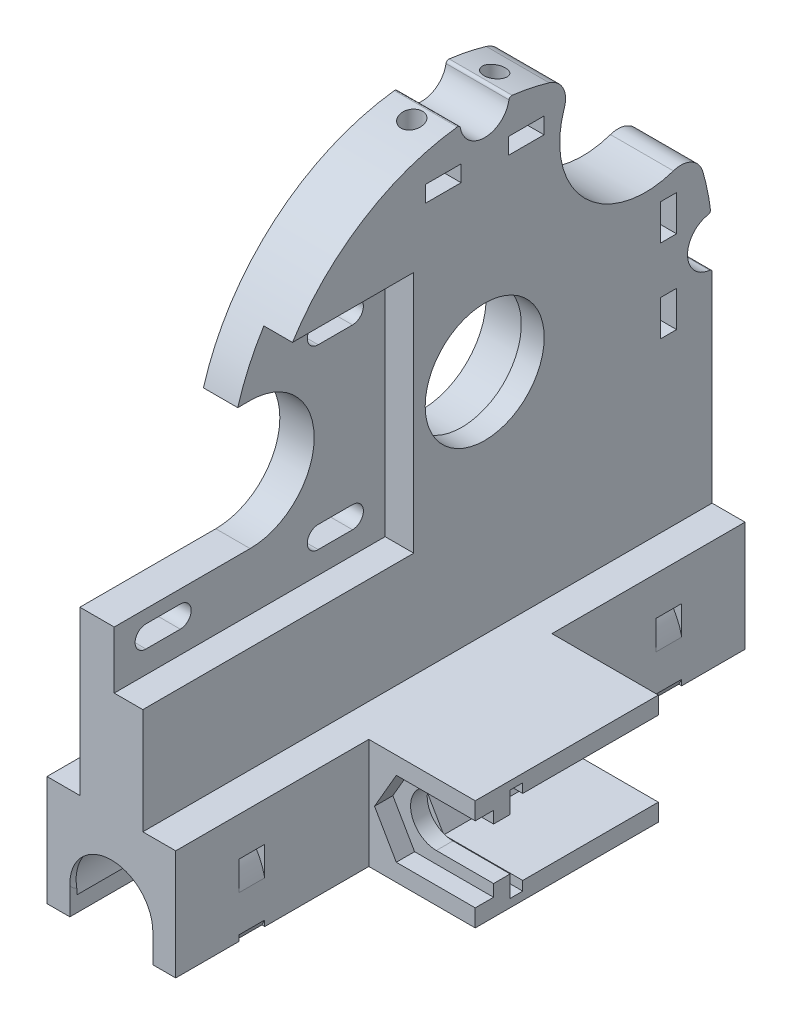
SolidWorks part; units mm, degrees
ref_plane "Alzado" through (0, 0, 0) normal (0, 0, 1) x (1, 0, 0)
ref_plane "Planta" through (0, 0, 0) normal (0, 1, 0) x (1, 0, 0)
ref_plane "Vista lateral" through (0, 0, 0) normal (1, 0, 0) x (0, 0, -1)
sketch "Croquis1" plane through (0, 0, 0) normal (1, 0, 0) x (0, 0, -1)
  line L0 (-14.1, 24.3) -> (-8.1, 24.3) construction
  line L2 (-26, 28.5) -> (-49.75, 28.5)
  line L3 (-49.75, 28.5) -> (-49.75, 0)
  line L4 (-49.75, 18.5) -> (-2.4, 18.5)
  line L5 (-2.4, 18.5) -> (-2.4, 61)
  line L6 (-2.4, 61) -> (-23.5932, 61)
  line L7 (20.375, 70.44) -> (14.125, 70.44)
  line L8 (-28.1541, 50.9002) -> (-26, 50.9002)
  line L9 (49.75, 0) -> (49.75, 34.9761)
  line L10 (-23.5932, 61) -> (-2.4, 61)
  line L11 (-2.4, 61) -> (-2.4, 18.5)
  line L12 (-2.4, 18.5) -> (-49.75, 18.5)
  line L13 (-14.1, 55.3) -> (-8.1, 55.3) construction
  line L14 (-49.75, 10) -> (49.75, 10)
  line L15 (-14.1, 57.2) -> (-8.1, 57.2)
  line L16 (-14.1, 53.4) -> (-8.1, 53.4)
  line L17 (20.375, 70.44) -> (20.375, 73.29)
  line L18 (-14.1, 26.2) -> (-8.1, 26.2)
  line L19 (-14.1, 22.4) -> (-8.1, 22.4)
  line L20 (20.375, 73.29) -> (14.125, 73.29)
  line L21 (14.125, 70.44) -> (14.125, 73.29)
  line L22 (-44.2, 24.3) -> (-38.2, 24.3) construction
  line L23 (-44.2, 26.2) -> (-38.2, 26.2)
  line L24 (-44.2, 22.4) -> (-38.2, 22.4)
  line L25 (49.75, 0) -> (-49.75, 0)
  line L26 (43.54, 50.125) -> (40.69, 50.125)
  line L27 (43.54, 50.125) -> (43.54, 43.875)
  line L28 (43.54, 43.875) -> (40.69, 43.875)
  line L29 (40.69, 50.125) -> (40.69, 43.875)
  line L30 (43.54, 50.125) -> (40.69, 43.875) construction
  line L31 (43.54, 43.875) -> (40.69, 50.125) construction
  line L32 (43.54, 29.375) -> (40.69, 29.375)
  line L33 (43.54, 29.375) -> (43.54, 35.625)
  line L34 (43.54, 35.625) -> (40.69, 35.625)
  line L35 (40.69, 29.375) -> (40.69, 35.625)
  line L36 (43.54, 29.375) -> (40.69, 35.625) construction
  line L37 (43.54, 35.625) -> (40.69, 29.375) construction
  line L38 (20.375, 70.44) -> (14.125, 73.29) construction
  line L39 (20.375, 73.29) -> (14.125, 70.44) construction
  line L40 (5.875, 73.29) -> (-0.375, 73.29)
  line L41 (5.875, 73.29) -> (5.875, 70.44)
  line L42 (5.875, 70.44) -> (-0.375, 70.44)
  line L43 (-0.375, 73.29) -> (-0.375, 70.44)
  line L44 (5.875, 73.29) -> (-0.375, 70.44) construction
  line L45 (5.875, 70.44) -> (-0.375, 73.29) construction
  arc A2 (-26, 28.5) -> (-26, 50.9002) centre (-26, 39.7001) ccw
  arc A3 (49.75, 34.9761) -> (49.3021, 35.4734) centre (49.25, 34.9761) ccw
  arc A4 (49.0453, 43.9919) -> (49.3021, 35.4734) centre (49.75, 39.75) ccw
  arc A5 (49.0453, 43.9919) -> (49.4597, 44.5454) centre (48.9633, 44.4851) ccw
  arc A6 (5.2046, 79.2097) -> (-28.1541, 50.9002) centre (10, 39.75) ccw
  arc A7 (14.7954, 79.2097) -> (14.2419, 78.7953) centre (14.7351, 78.7133) ccw
  arc A8 (5.7581, 78.7953) -> (14.2419, 78.7953) centre (10, 79.5) ccw
  arc A9 (5.7581, 78.7953) -> (5.2046, 79.2097) centre (5.2649, 78.7133) ccw
  arc A10 (49.4597, 44.5454) -> (14.7954, 79.2097) centre (10, 39.75) ccw
  arc A11 (-14.1, 57.2) -> (-14.1, 53.4) centre (-14.1, 55.3) ccw
  arc A12 (-8.1, 53.4) -> (-8.1, 57.2) centre (-8.1, 55.3) ccw
  arc A13 (-14.1, 26.2) -> (-14.1, 22.4) centre (-14.1, 24.3) ccw
  arc A14 (-8.1, 22.4) -> (-8.1, 26.2) centre (-8.1, 24.3) ccw
  arc A15 (-44.2, 26.2) -> (-44.2, 22.4) centre (-44.2, 24.3) ccw
  arc A16 (-38.2, 22.4) -> (-38.2, 26.2) centre (-38.2, 24.3) ccw
  circle A17 centre (10, 39.75) radius 10.4
  point P0 (2.75, 71.865)
  point P1 (17.25, 71.865)
  point P3 (42.115, 47)
  point P4 (42.115, 32.5)
  point P5 (17.25, 71.865)
  point P11 (42.115, 32.5)
  point P31 (-11.1, 55.3)
  point P39 (-11.1, 24.3)
  point P44 (-8.1, 55.3)
  point P45 (-44.2, 24.3)
  point P46 (-38.2, 24.3)
  point P47 (-41.2, 24.3)
  point P51 (-14.1, 55.3)
  point P59 (42.115, 47)
  point P75 (2.75, 71.865)
  dimension "D9" = 0.5
  dimension "D11" = 10
  dimension "D12" = 10
  dimension "D13" = 39.75
  dimension "D14" = 42.5
  dimension "D15" = 11.2001
  dimension "D16" = 2.85
  dimension "D17" = 39.75
  dimension "D26" = 0.5
  dimension "D28" = 1.9
  dimension "D29" = 31
  dimension "D30" = 30.1
  dimension "D32" = 5.8
  dimension "D35" = 14.5
  dimension "D38" = 7.635
  dimension "D39" = 7.25
  dimension "D40" = 36
  dimension "D5" = 20.8
  dimension "D10" = 0.5
  dimension "D6" = 39.75
  dimension "D7" = 39.75
  dimension "D8" = 4.3
  dimension "D19" = 1.9
  dimension "D22" = 4.3
  dimension "D27" = 0.5
  dimension "D31" = 1.9
  dimension "D23" = 6.25
  dimension "D1" = 10
  dimension "D3" = 42.5
  dimension "D4" = 12.4
  dimension "D18" = 5.7
  dimension "D20" = 6
  dimension "D21" = 5.8
  dimension "D24" = 99.5
  dimension "D33" = 6
  dimension "D34" = 6
  dimension "D36" = 2.85
  dimension "D37" = 6.25
  dimension "D41" = 6.25
  dimension "D42" = 2.85
  dimension "D43" = 6.25
  dimension "D44" = 2.85
  dimension "D45" = 14.5
  dimension "D46" = 7.25
  dimension "D47" = 7.635
extrude "Saliente-Extruir1" add sketch "Croquis1" along normal blind 11 contours A9 A4 A5 A7 A8 | L25 L9 L14 L3 region at (0, 17.2879, 26.075) region at (0, 5, 0)
extrude "Saliente-Extruir2" add sketch "Croquis1<3>" along normal blind 6 contours L8 L2 region at (0, 39.7001, 14.1637)
sketch "Croquis1<3>" plane through (0, 0, 0) normal (1, 0, 0) x (0, 0, -1) same geometry as "Croquis1"
sketch "Croquis2" plane through (0, 0, 0) normal (-1, 0, 0) x (0, 0, 1)
  circle A0 centre (-10, 39.75) radius 11.25
  dimension "D1" = 22.5
extrude "Cortar-Extruir1" cut sketch "Croquis2" against normal blind 7
sketch "Croquis3" plane through (0, 0, -49.75) normal (0, 0, -1) x (-1, 0, 0)
  line L0 (0, 35.4734) -> (0, 43.9919) construction
  line L1 (-11, 34.9761) -> (0, 34.9761) construction
  line L2 (-11, 44.5454) -> (0, 44.5454) construction
  circle A0 centre (-5.5, 46.9826) radius 1.875
  circle A1 centre (-5.5, 32.4826) radius 1.875
  point P6 (0, 39.7326)
  point P11 (-5.5, 44.5454)
  point P15 (-5.5, 34.9761)
  dimension "D1" = 14.5
  dimension "D3" = 3.75
  dimension "D2" = 7.25
extrude "Cortar-Extruir2" cut sketch "Croquis3" against normal blind 20
ref_plane "Plano1" through (0, 79.2097, 0) normal (0, 1, 0) x (1, 0, 0)
sketch "Croquis4" plane through (0, 79.2097, 0) normal (0, 1, 0) x (1, 0, 0)
  line L0 (0, 14.2419) -> (0, 5.7581) construction
  line L1 (11, 14.7954) -> (0, 14.7954) construction
  circle A0 centre (5.5, 2.75) radius 1.875
  circle A1 centre (5.5, 17.25) radius 1.875
  point P6 (0, 10)
  point P10 (5.5, 14.7954)
  dimension "D1" = 3.75
  dimension "D2" = 14.5
  dimension "D3" = 7.25
extrude "Cortar-Extruir3" cut sketch "Croquis4" against normal blind 20 contours A0 | A1
sketch "Croquis5" plane through (0, 0, -40.69) normal (0, 0, -1) x (-1, 0, 0)
  line L0 (0, 29.375) -> (0, 35.625) construction
  line L1 (-3.7, 50.1003) -> (-7.3, 50.1003) construction
  line L2 (-7.3, 50.1003) -> (-9.1, 46.9826) construction
  line L3 (-9.1, 46.9826) -> (-7.3, 43.8649) construction
  line L4 (-7.3, 43.8649) -> (-3.578, 43.8649) construction
  line L5 (-3.6942, 43.875) -> (-1.9, 46.9826)
  line L6 (-1.9, 46.9826) -> (-3.7143, 50.125)
  line L7 (-3.7, 35.6003) -> (-7.3, 35.6003) construction
  line L8 (-7.3, 35.6003) -> (-9.1, 32.4826) construction
  line L9 (-9.1, 32.4826) -> (-7.3, 29.3649) construction
  line L10 (-7.3, 29.3649) -> (-3.5459, 29.3649) construction
  line L11 (-3.6942, 29.375) -> (-1.9, 32.4826)
  line L12 (-1.9, 32.4826) -> (-3.7143, 35.625)
  line L13 (0, 35.625) -> (-11, 35.625) construction
  line L14 (-11, 35.625) -> (-11, 29.375) construction
  line L15 (-11, 29.375) -> (0, 29.375) construction
  line L16 (0, 43.875) -> (0, 50.125) construction
  line L17 (0, 50.125) -> (-11, 50.125) construction
  line L18 (-11, 50.125) -> (-11, 43.875) construction
  line L19 (-11, 43.875) -> (0, 43.875) construction
  line L20 (0, 29.375) -> (0, 35.625)
  line L21 (0, 35.625) -> (-11, 35.625)
  line L22 (-11, 35.625) -> (-11, 29.375)
  line L23 (-11, 29.375) -> (0, 29.375)
  line L24 (0, 43.875) -> (0, 50.125)
  line L25 (0, 50.125) -> (-11, 50.125)
  line L26 (-11, 50.125) -> (-11, 43.875)
  line L27 (-11, 43.875) -> (0, 43.875)
  circle A0 centre (-5.5, 46.9826) radius 3.1177 construction
  circle A1 centre (-5.5, 32.4826) radius 3.1177 construction
  line M10 (0, 43.875) -> (0, 50.125)
  line M11 (0, 50.125) -> (-11, 50.125)
  line M13 (-11, 43.875) -> (0, 43.875)
  dimension "D1" = 3.6
  dimension "D2" = 3.6
extrude "Saliente-Extruir4" add sketch "Croquis5" along normal up to vertex (2.85 mm away) contours L6 L5 M13 M10 M11 | L11 L23 L20 L21 L12 region at (1.4495, 47.0056, -40.69) region at (1.4495, 32.5056, -40.69) up to point (0, 29.375, -43.54)
sketch "Croquis6" plane through (0, 70.44, 0) normal (0, 1, 0) x (1, 0, 0)
  line L0 (0, 20.375) -> (0, 14.125) construction
  line L1 (1.9, 2.75) -> (3.7042, -0.375)
  line L2 (3.7, -0.3677) -> (7.3, -0.3677) construction
  line L3 (7.3, -0.3677) -> (9.1, 2.75) construction
  line L4 (9.1, 2.75) -> (7.3, 5.8677) construction
  line L5 (7.3, 5.8677) -> (3.5459, 5.8677) construction
  line L6 (3.7042, 5.875) -> (1.9, 2.75)
  line L7 (7.3, 14.1323) -> (9.1, 17.25) construction
  line L8 (9.1, 17.25) -> (7.3, 20.3677) construction
  line L9 (7.3, 20.3677) -> (3.578, 20.3677) construction
  line L10 (3.7042, 20.375) -> (1.9, 17.25)
  line L11 (1.9, 17.25) -> (3.7042, 14.125)
  line L12 (3.7, 14.1323) -> (7.3, 14.1323) construction
  line L13 (0, 14.125) -> (11, 14.125) construction
  line L14 (11, 14.125) -> (11, 20.375) construction
  line L15 (11, 20.375) -> (0, 20.375) construction
  line L16 (0, 5.875) -> (0, -0.375) construction
  line L17 (0, -0.375) -> (11, -0.375) construction
  line L18 (11, -0.375) -> (11, 5.875) construction
  line L19 (11, 5.875) -> (0, 5.875) construction
  line L20 (0, 20.375) -> (0, 14.125)
  line L21 (0, 14.125) -> (11, 14.125)
  line L22 (11, 14.125) -> (11, 20.375)
  line L23 (11, 20.375) -> (0, 20.375)
  line L24 (0, 5.875) -> (0, -0.375)
  line L25 (0, -0.375) -> (11, -0.375)
  line L26 (11, -0.375) -> (11, 5.875)
  line L27 (11, 5.875) -> (0, 5.875)
  circle A0 centre (5.5, 2.75) radius 3.1177 construction
  circle A1 centre (5.5, 17.25) radius 3.1177 construction
  line M8 (0, 5.875) -> (0, -0.375)
  line M9 (0, -0.375) -> (11, -0.375)
  line M11 (11, 5.875) -> (0, 5.875)
  dimension "D1" = 3.6
  dimension "D2" = 3.6
extrude "Saliente-Extruir5" add sketch "Croquis6" along normal up to vertex (2.85 mm away) contours L6 L1 M11 M8 M9 | L10 L23 L20 L21 L11 region at (1.4495, 70.44, -2.75) region at (1.4495, 70.44, -17.25) up to point (0, 73.29, -14.125)
sketch "Croquis7" plane through (0, 0, 0) normal (0, 0, 1) x (1, 0, 0)
  line L0 (-1.75, -19.25) -> (-5.75, -19.25)
  line L1 (5.5, -14.25) -> (5.5, -5) construction
  line L2 (-1.75, -14.25) -> (-1.75, -19.25)
  line L3 (12.75, -19.25) -> (12.75, -14.25)
  line L4 (12.75, -19.25) -> (16.75, -19.25)
  line L5 (16.75, -19.25) -> (16.75, 0)
  line L6 (-5.75, 0) -> (16.75, 0)
  line L7 (-5.75, -19.25) -> (-5.75, 0)
  line L9 (11, 0) -> (0, 0) construction
  arc A0 (12.75, -14.25) -> (-1.75, -14.25) centre (5.5, -14.25) ccw
  point P15 (5.5, 0)
  dimension "D1" = 7.25
  dimension "D2" = 19.25
  dimension "D3" = 5
  dimension "D4" = 4
  dimension "D5" = 14.5
extrude "Saliente-Extruir6" add sketch "Croquis7" against normal up to surface and the other way up to surface up to face at (5.5, 34.3576, -49.75) other way up to face at (5.6667, 15.6667, 49.75)
ref_plane "Plano2" through (0, -14.25, 0) normal (0, -1, 0) x (-1, 0, 0)
sketch "Croquis8" plane through (0, -14.25, 0) normal (0, -1, 0) x (-1, 0, 0)
  line L0 (-12.75, 23.134) -> (-5.5, 23.134)
  line L1 (-5.5, 23.134) -> (-5.5, 49.75)
  line L2 (-5.5, 49.75) -> (-12.75, 49.75)
  line L3 (-12.75, 49.75) -> (-12.8639, 48.542)
  line L4 (-12.8639, 48.542) -> (-13.1, 48.542)
  line L5 (-13.1, 48.542) -> (-13.1, 24.342)
  line L6 (-13.1, 24.342) -> (-12.8639, 24.342)
  line L7 (-12.8639, 24.342) -> (-12.75, 23.134)
  line L8 (-5.5, 23.134) -> (-5.5, 49.75) construction
  line L9 (-5.5, 49.75) -> (-5.5, -49.75) construction
  line L10 (1.75, 49.75) -> (-12.75, 49.75) construction
  line L11 (-12.75, -49.75) -> (1.75, -49.75) construction
  line L12 (-16.75, 49.75) -> (-12.75, 49.75) construction
  point P8 (-5.5, 23.134)
  point P9 (-5.5, 36.442)
  point P20 (-13.1, 36.442)
  dimension "D1" = 7.25
  dimension "D2" = 7.25
  dimension "D3" = 7.6
  dimension "D4" = 0.2361
  dimension "D5" = 1.208
  dimension "D6" = 24.2
  dimension "D7" = 26.616
  dimension "D8" = 0.2361
revolve "Cortar-Revolución1" cut sketch "Croquis8" angle 360 about L1
mirror "Simetría1" about plane through (0, 0, 0) normal (0, 0, 1) of "Cortar-Revolución1"
ref_plane "Plano3" through (0, 0, -36.442) normal (0, 0, -1) x (-1, 0, 0)
sketch "Croquis9" plane through (0, 0, -36.442) normal (0, 0, -1) x (-1, 0, 0)
  line L0 (-16.75, -6.7876) -> (-16.75, -11.8652)
  line L1 (5.75, -11.8652) -> (5.75, -6.7876)
  line L2 (5.75, -18.25) -> (5.25, -19.25)
  line L3 (5.75, -18.25) -> (5.75, -19.25)
  line L4 (5.75, -19.25) -> (5.25, -19.25)
  line L5 (5.75, -19.25) -> (5.75, 0) construction
  line L6 (-5.5, -14.25) -> (-5.5, -16.8296) construction
  line L7 (-16.75, -19.25) -> (-16.25, -19.25)
  line L8 (-16.75, -18.25) -> (-16.75, -19.25)
  line L9 (-16.75, -18.25) -> (-16.25, -19.25)
  line L10 (1.75, -19.25) -> (5.75, -19.25) construction
  arc A0 (-16.75, -11.8652) -> (5.75, -11.8652) centre (-5.5, -14.25) cw
  arc A1 (5.75, -6.7876) -> (-16.75, -6.7876) centre (-5.5, -14.25) ccw
  arc A2 (1.75, -14.25) -> (-12.75, -14.25) centre (-5.5, -14.25) ccw construction
  point P12 (5.75, -19.25)
  dimension "D1" = 11.5
  dimension "D2" = 13.5
  dimension "D3" = 5.0776
  dimension "D4" = 0.5
  dimension "D5" = 1
extrude "Cortar-Extruir4" cut sketch "Croquis9" against normal mid plane 4.5
mirror "Simetría2" about plane through (0, 0, 0) normal (0, 0, 1) of "Cortar-Extruir4"
sketch "Croquis10" plane through (16.75, 0, 0) normal (1, 0, 0) x (0, 0, -1)
  line L1 (-16, 0) -> (16, 0)
  line L2 (-16, 0) -> (-16, -19.25)
  line L3 (-16, -19.25) -> (16, -19.25)
  line L4 (16, 0) -> (16, -19.25)
  line L5 (-16, 0) -> (16, -19.25) construction
  line L6 (-16, -19.25) -> (16, 0) construction
  line L9 (49.75, 0) -> (49.75, -19.25) construction
  line L10 (49.75, 0) -> (-49.75, 0) construction
  point P0 (0, -9.625)
  point P14 (49.75, -9.625)
  dimension "D2" = 32
extrude "Saliente-Extruir7" add sketch "Croquis10" along normal blind 18.6 contours L4 L3 L2 L1
ref_plane "Plano4" through (0, 0, 12.8) normal (0, 0, 1) x (1, 0, 0)
sketch "Croquis11" plane through (0, 0, 12.8) normal (0, 0, 1) x (1, 0, 0)
  line L0 (21.5505, -3.043) -> (35.35, -3.043)
  line L1 (35.35, -3.043) -> (35.35, -16.207)
  line L2 (21.5505, -16.207) -> (35.35, -16.207)
  line L3 (25.35, -5.125) -> (35.35, -5.125)
  line L4 (25.35, -14.125) -> (35.35, -14.125)
  line L5 (35.35, 0) -> (35.35, -19.25) construction
  line L8 (17.7504, -9.625) -> (21.5505, -3.043)
  line L9 (21.5505, -16.207) -> (17.7504, -9.625)
  arc A1 (25.35, -14.125) -> (25.35, -5.125) centre (25.35, -9.625) cw
  point P5 (35.35, -9.625)
  point P14 (35.35, -5.125)
  point P16 (35.35, -14.125)
  dimension "D4" = 25.35
  dimension "D1" = 4.5
  dimension "D2" = 17.7504
  dimension "D3" = 21.5505
  dimension "D5" = 3.043
extrude "Cortar-Extruir5" cut sketch "Croquis11" against normal through all both and the other way through all contours L1 | L1 | A1 L4 L1 L3 | L4 A1 L3 L1 L0 L8 L9 L2 region at (28.4502, -3.2628, 12.8) region at (28.5456, -9.625, 12.8)
extrude "Saliente-Extruir8" add sketch "Croquis11<3>" against normal blind 2.9 contours L1 | L4 A1 L3 L1 L0 L8 L9 L2 region at (28.4502, -3.2628, 12.8)
sketch "Croquis11<3>" plane through (0, 0, 12.8) normal (0, 0, 1) x (1, 0, 0) same geometry as "Croquis11"
sketch "Croquis13" plane through (0, 0, 9.9) normal (0, 0, -1) x (-1, 0, 0)
  line L2 (-35.35, -17.825) -> (-25.35, -17.825)
  line L3 (-25.35, -1.425) -> (-35.35, -1.425)
  line L8 (-35.35, -16.207) -> (-35.35, -19.25) construction
  line L11 (-25.35, -14.125) -> (-35.35, -14.125)
  line L12 (-35.35, -5.125) -> (-25.35, -5.125)
  line L13 (-35.35, -3.043) -> (-35.35, -5.125)
  line L14 (-21.5505, -3.043) -> (-35.35, -3.043)
  line L15 (-17.7504, -9.625) -> (-21.5505, -3.043)
  line L16 (-21.5505, -16.207) -> (-17.7504, -9.625)
  line L17 (-35.35, -16.207) -> (-21.5505, -16.207)
  line L18 (-35.35, -14.125) -> (-35.35, -16.207)
  line L19 (-25.35, -14.125) -> (-35.35, -14.125)
  line L20 (-35.35, -5.125) -> (-25.35, -5.125)
  line L21 (-35.35, -1.425) -> (-35.35, -5.125)
  line L22 (-21.5505, -3.043) -> (-35.35, -3.043)
  line L23 (-17.7504, -9.625) -> (-21.5505, -3.043)
  line L24 (-21.5505, -16.207) -> (-17.7504, -9.625)
  line L25 (-35.35, -16.207) -> (-21.5505, -16.207)
  line L26 (-35.35, -14.125) -> (-35.35, -17.825)
  arc A1 (-25.35, -1.425) -> (-25.35, -17.825) centre (-25.35, -9.625) cw
  arc A2 (-25.35, -14.125) -> (-25.35, -5.125) centre (-25.35, -9.625) ccw
  arc A3 (-25.35, -14.125) -> (-25.35, -5.125) centre (-25.35, -9.625) ccw
  dimension "D2" = 8.2
  dimension "D1" = 0
extrude "Cortar-Extruir7" cut sketch "Croquis13" along normal blind 2.2 contours A1 L3 L2 region at (35.105, -17.016, 9.9)
sketch "Croquis14" plane through (11, 0, 0) normal (1, 0, 0) x (0, 0, -1)
  circle A0 centre (38.1075, 67.8575) radius 15
  arc A1 (49.4597, 44.5454) -> (14.7954, 79.2097) centre (10, 39.75) ccw construction
  dimension "D1" = 30
extrude "Cortar-Extruir8" cut sketch "Croquis14" against normal through all
fillet "Redondeo1" radius 4 2 edges at (5.5, 55.4402, -46.5223) (5.5, 76.2723, -25.6902)
